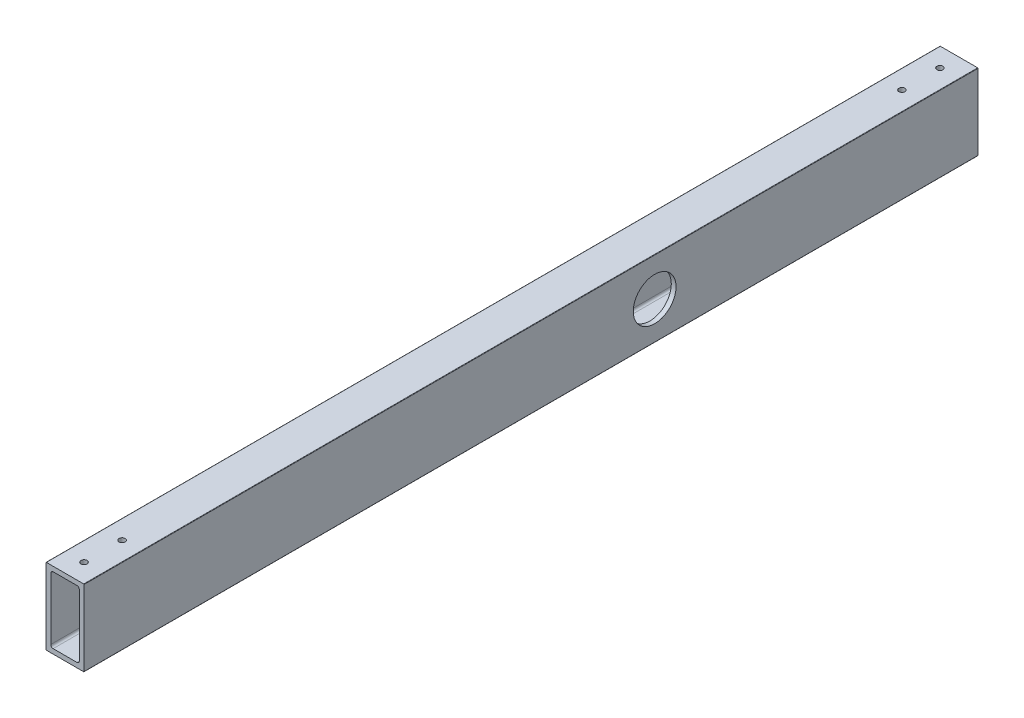
SolidWorks part; units mm, degrees
material "3.0205 (EN-AW 1200)"
ref_plane "Front Plane" through (0, 0, 0) normal (0, 0, 1) x (1, 0, 0)
ref_plane "Top Plane" through (0, 0, 0) normal (0, 1, 0) x (1, 0, 0)
ref_plane "Right Plane" through (0, 0, 0) normal (1, 0, 0) x (0, 0, -1)
ref_plane "Plane1" through (0, 0, 0) normal (0, 0, -1) x (-1, 0, 0)
sketch "Sketch1" plane through (0, 0, 0) normal (0, 0, -1) x (-1, 0, 0)
  line L0 (-3.175, 46.0375) -> (-3.175, 4.7625)
  line L1 (-4.7625, 3.175) -> (-20.6375, 3.175)
  line L2 (-22.225, 4.7625) -> (-22.225, 46.0375)
  line L3 (-20.6375, 47.625) -> (-4.7625, 47.625)
  line L4 (0, 0.254) -> (0, 50.546)
  line L5 (-0.254, 50.8) -> (-25.146, 50.8)
  line L6 (-25.4, 50.546) -> (-25.4, 0.254)
  line L7 (-25.146, 0) -> (-0.254, 0)
  arc A0 (-3.175, 4.7625) -> (-4.7625, 3.175) centre (-4.7625, 4.7625) cw
  arc A1 (-20.6375, 3.175) -> (-22.225, 4.7625) centre (-20.6375, 4.7625) cw
  arc A2 (-22.225, 46.0375) -> (-20.6375, 47.625) centre (-20.6375, 46.0375) cw
  arc A3 (-4.7625, 47.625) -> (-3.175, 46.0375) centre (-4.7625, 46.0375) cw
  arc A4 (-0.254, 0) -> (0, 0.254) centre (-0.254, 0.254) ccw
  arc A5 (0, 50.546) -> (-0.254, 50.8) centre (-0.254, 50.546) ccw
  arc A6 (-25.146, 50.8) -> (-25.4, 50.546) centre (-25.146, 50.546) ccw
  arc A7 (-25.4, 0.254) -> (-25.146, 0) centre (-25.146, 0.254) ccw
extrude "Boss-Extrude1" add sketch "Sketch1" against normal blind 596.9
sketch "Sketch2" plane through (0, 50.8, 0) normal (0, 1, 0) x (1, 0, 0)
  line L0 (0.254, -596.9) -> (25.146, -596.9) construction
  line L1 (25.146, -298.45) -> (0, -298.45) construction
  line L2 (25.146, -596.9) -> (25.146, 0) construction
  line L3 (0, -596.9) -> (0, 0) construction
  circle A0 centre (12.7, -584.2) radius 2.032
  circle A1 centre (12.7, -558.8) radius 2.032
  circle A2 centre (12.7, -38.1) radius 2.032
  circle A3 centre (12.7, -12.7) radius 2.032
  dimension "D1" = 4.064
  dimension "D2" = 4.064
  dimension "D3" = 12.7
  dimension "D4" = 25.4
extrude "Cut-Extrude1" cut sketch "Sketch2" against normal through all
ref_plane "Plane2" through (224.155, 46.0375, 596.9) normal (0, 0, -1) x (-1, 0, 0)
sketch "Sketch5" plane through (25.4, 0, 0) normal (1, 0, 0) x (0, 0, -1)
  line L0 (-596.9, 50.546) -> (0, 50.546) construction
  line L2 (0, 50.546) -> (0, 0.254) construction
  circle A0 centre (-215.9, 25.146) radius 14.2875
  dimension "D1" = 28.575
  dimension "D2" = 25.4
  dimension "D3" = 215.9
extrude "Cut-Extrude2" cut sketch "Sketch5" against normal through all
